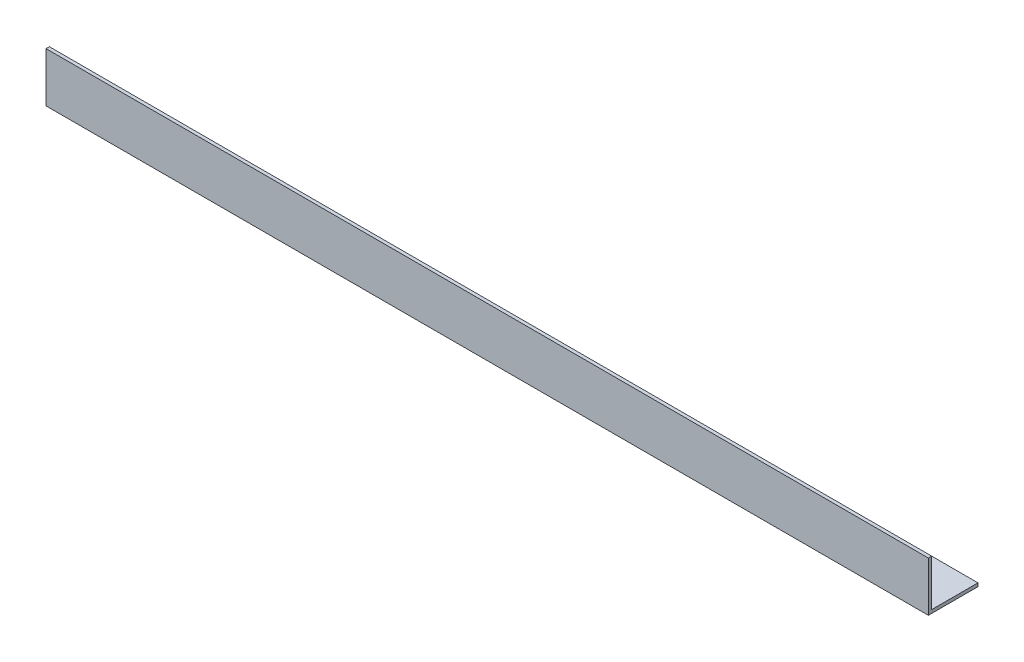
SolidWorks part; units mm, degrees
ref_plane "Спереди" through (0, 0, 0) normal (0, 0, 1) x (1, 0, 0)
ref_plane "Сверху" through (0, 0, 0) normal (0, 1, 0) x (1, 0, 0)
ref_plane "Справа" through (0, 0, 0) normal (1, 0, 0) x (0, 0, -1)
sketch "Эскиз1" plane through (0, 0, 0) normal (1, 0, 0) x (0, 0, -1)
  line L0 (0, 0) -> (0, 45)
  line L1 (0, 0) -> (45, 0)
extrude "Вытянуть-Тонкостенный1" add sketch "Эскиз1" along normal blind 800 thin thin type one direction reverse wall 3
